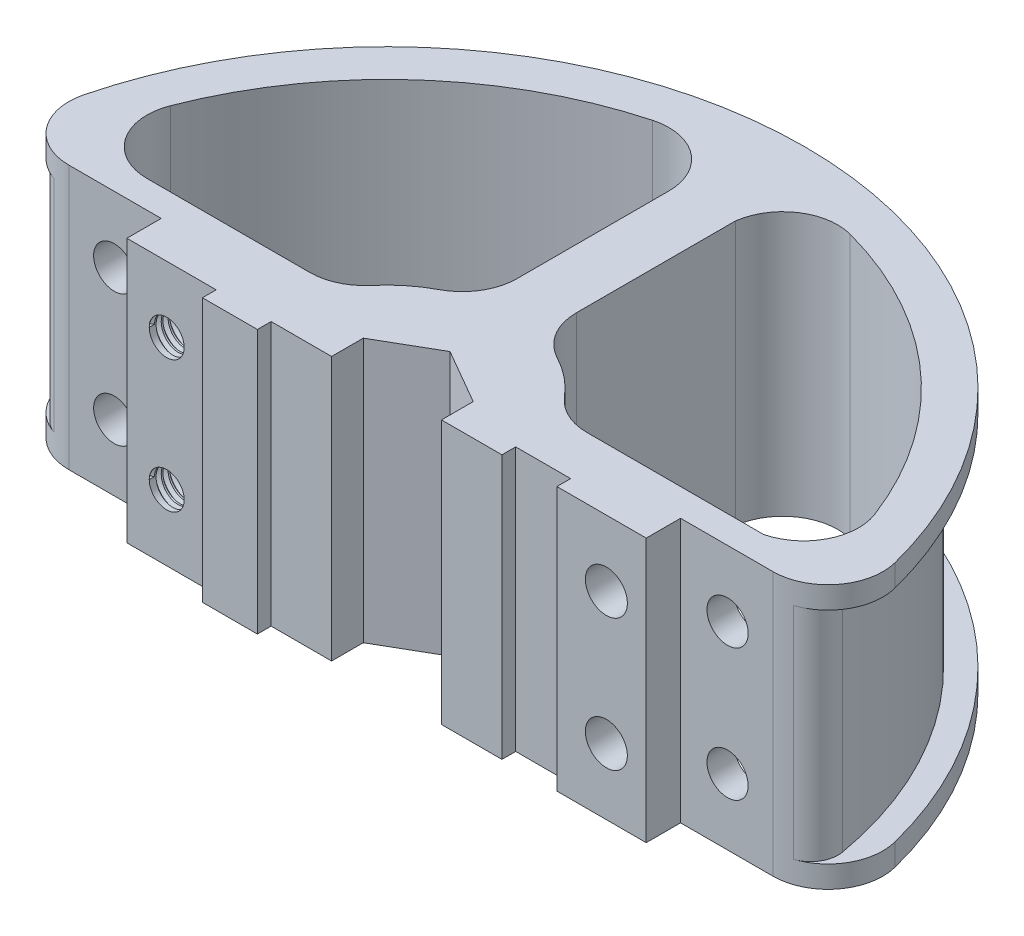
SolidWorks part; units mm, degrees
ref_plane "Front Plane" through (0, 0, 0) normal (0, 0, 1) x (1, 0, 0)
ref_plane "Top Plane" through (0, 0, 0) normal (0, 1, 0) x (1, 0, 0)
ref_plane "Right Plane" through (0, 0, 0) normal (1, 0, 0) x (0, 0, -1)
sketch "Sketch1" plane through (0, 0, 0) normal (0, 1, 0) x (1, 0, 0)
  line L2 (19.685, 0) -> (19.685, 1.5875)
  line L3 (-30.0038, 3.9688) -> (-40.6854, 3.9687)
  line L5 (0, 7.3323) -> (-6.35, 3.6662)
  line L6 (-6.35, 3.6662) -> (-6.35, 0)
  line L9 (6.35, 0) -> (6.35, 3.6662)
  line L10 (6.35, 3.6662) -> (0, 7.3323)
  line L12 (30.0037, 3.9688) -> (40.6854, 3.9688)
  line L13 (-30.0038, 0) -> (-30.0038, 3.9688)
  line L14 (-34.8254, 7.1437) -> (-16.0133, 7.1438)
  line L15 (-3.4223, 36.0471) -> (-3.4223, 18.5205)
  line L16 (3.4223, 36.8893) -> (3.4223, 18.5205)
  line L17 (36.4146, 7.1438) -> (16.0133, 7.1437)
  line L18 (-6.35, 0) -> (-13.335, 0)
  line L19 (6.35, 0) -> (13.335, 0)
  line L20 (-19.685, 0) -> (-19.685, -1.5875)
  line L21 (-19.685, -1.5875) -> (-13.335, -1.5875)
  line L22 (-13.335, -1.5875) -> (-13.335, 0)
  line L23 (-19.685, 0) -> (-30.0038, 0)
  line L26 (13.335, 0) -> (13.335, 1.5875)
  line L27 (13.335, 1.5875) -> (19.685, 1.5875)
  line L28 (19.685, 1.5875) -> (19.685, 0)
  line L29 (19.685, 0) -> (30.0037, 0)
  line L30 (-6.35, -3.6662) -> (0, -7.3323) [skipped]
  line L31 (0, -7.3323) -> (3.175, -5.4993) [skipped]
  line L32 (30.0037, 0) -> (30.0037, 3.9688)
  arc A1 (-11.4338, 42.1759) -> (-40.7465, 15.788) centre (0, 0) ccw
  arc A2 (3.4223, 36.8893) -> (11.3704, 42.193) centre (9.7181, 36.0618) cw
  arc A3 (-3.4223, 36.0471) -> (-11.4338, 42.1759) centre (-9.7723, 36.0471) ccw
  arc A5 (6.35, 0) -> (-6.35, 0) centre (0, 0) ccw construction
  arc A8 (-34.8254, 7.1437) -> (-40.7465, 15.788) centre (-34.8254, 13.4937) cw
  arc A9 (40.8294, 15.5725) -> (11.3704, 42.193) centre (0, 0) ccw
  arc A10 (36.4146, 7.1438) -> (40.8294, 15.5725) centre (34.8963, 13.3095) ccw
  arc A15 (-11.4338, 42.1759) -> (-40.7465, 15.788) centre (0, 0) ccw
  arc A16 (11.1574, 9.4019) -> (6.8089, 12.9044) centre (0, 0) ccw
  arc A17 (-6.8089, 12.9044) -> (-11.1574, 9.4019) centre (0, 0) ccw
  arc A18 (16.0133, 7.1437) -> (11.1574, 9.4019) centre (16.0133, 13.4937) cw
  arc A19 (3.4223, 18.5205) -> (6.8089, 12.9044) centre (9.7723, 18.5205) ccw
  arc A20 (-3.4223, 18.5205) -> (-6.8089, 12.9044) centre (-9.7723, 18.5205) cw
  arc A21 (-16.0133, 7.1438) -> (-11.1574, 9.4019) centre (-16.0133, 13.4938) ccw
  arc A24 (46.8405, 11.8798) -> (-46.8405, 11.8798) centre (0, 0) ccw
  arc A25 (46.8405, 11.8798) -> (40.6854, 3.9688) centre (40.6854, 10.3188) cw
  arc A26 (-40.6854, 3.9687) -> (-46.8405, 11.8798) centre (-40.6854, 10.3187) cw
  point P30 (43.5089, 4.0642)
  point P33 (-3.4223, 14.1835)
  point P35 (18.1219, 7.1437)
  point P36 (-48.3235, 0)
  dimension "D1" = 6.35
  dimension "D2" = 6.35
  dimension "D4" = 6.35
  dimension "D5" = 6.35
  dimension "D6" = 6.35
  dimension "D7" = 48.3235
  dimension "D8" = 7.1437
  dimension "D3" = 12.7
extrude "Boss-Extrude1" add sketch "Sketch1" along normal blind 30.48 contours A26 L3 L13 L23 L20 L21 L22 L18 L6 L5 L10 L9 L19 L26 L27 L2 L29 L32 L12 A25 A24 A21 L14 A8 A1 A3 L15 A20 A17 A19 L16 A2 A9 A10 L17 A18 A16 region at (-0.2716, 0, -20.5788)
sketch "Sketch4" plane through (0, 0, 0) normal (0, 0, 1) x (1, 0, 0)
  line L6 (-45.5114, 27.94) -> (-45.5114, 2.54)
  line L8 (-45.5114, 27.94) -> (-56.4907, 27.94)
  line L9 (-56.4907, 27.94) -> (-56.4907, 2.54)
  line L10 (-56.4907, 2.54) -> (-45.5114, 2.54)
  line L11 (0, -4.3574) -> (0, 34.0125)
revolve "Cut-Revolve1" cut sketch "Sketch4" angle 360 about L11 region at (-51.001, 15.24, 0)
fillet "Fillet2" radius 3.175 2 edges at (-45.141, 15.24, -5.7944) (45.141, 15.24, -5.7944)
sketch "Sketch5" plane through (0, 0, 0) normal (0, 0, 1) x (1, 0, 0)
  circle A2 centre (-35.433, 22.86) radius 2.3812
  circle A3 centre (-35.433, 7.62) radius 2.3812
  circle A4 centre (35.433, 22.86) radius 2.3812
  circle A5 centre (35.433, 7.62) radius 2.3812
extrude "Cut-Extrude1" cut sketch "Sketch5" against normal blind 12.7
sketch "Sketch6" plane through (0, 0, 0) normal (0, 0, 1) x (1, 0, 0)
  circle A0 centre (-25.4, 22.86) radius 2.0193
  circle A1 centre (-25.4, 7.62) radius 2.0193
  circle A2 centre (25.4, 7.62) radius 2.4257
  circle A3 centre (25.4, 22.86) radius 2.4257
  dimension "D1" = 4.0386
  dimension "D2" = 4.8514
extrude "Cut-Extrude2" cut sketch "Sketch6" against normal blind 12.7
thread "Thread1" pitch 0.7937 method cut profile "Thread Profile1" start angle 0, offset 0, length 10, pitch 0.7937, diameter 4.0386
ref_plane "Plane1" through (-27.4193, 22.86, 0) normal (0, -1, 0) x (-1, 0, 0)
sketch "Thread Profile1" plane through (-27.4193, 22.86, 0) normal (0, -1, 0) x (-1, 0, 0)
  line L0 (0, 0) -> (0, 0.7937) construction
  line L1 (0, 0) -> (0.4296, 0.248)
  line L2 (0.4296, 0.248) -> (0.4296, 0.3473)
  line L3 (0.4296, 0.3473) -> (0, 0.5953)
  line L4 (0.4296, 0.2977) -> (0, 0.2977) construction
  line L11 (0, 0) -> (0, 0.5953)
  point P2 (0, 0)
  dimension "Pitch" = 0.7937
  dimension "Profile_Angle" = 60
  dimension "Profile_Land" = 0.0992
  dimension "Profile_Height" = 0.4296
thread "Thread2" pitch 0.7937 method cut profile "Thread Profile2" start angle 0, offset 0, length 10, pitch 0.7937, diameter 4.0386
ref_plane "Plane2" through (-27.4193, 7.62, 0) normal (0, -1, 0) x (-1, 0, 0)
sketch "Thread Profile2" plane through (-27.4193, 7.62, 0) normal (0, -1, 0) x (-1, 0, 0)
  line L0 (0, 0) -> (0, 0.7937) construction
  line L1 (0, 0) -> (0.4296, 0.248)
  line L2 (0.4296, 0.248) -> (0.4296, 0.3473)
  line L3 (0.4296, 0.3473) -> (0, 0.5953)
  line L4 (0.4296, 0.2977) -> (0, 0.2977) construction
  line L11 (0, 0) -> (0, 0.5953)
  point P2 (0, 0)
  dimension "Pitch" = 0.7937
  dimension "Profile_Angle" = 60
  dimension "Profile_Land" = 0.0992
  dimension "Profile_Height" = 0.4296
